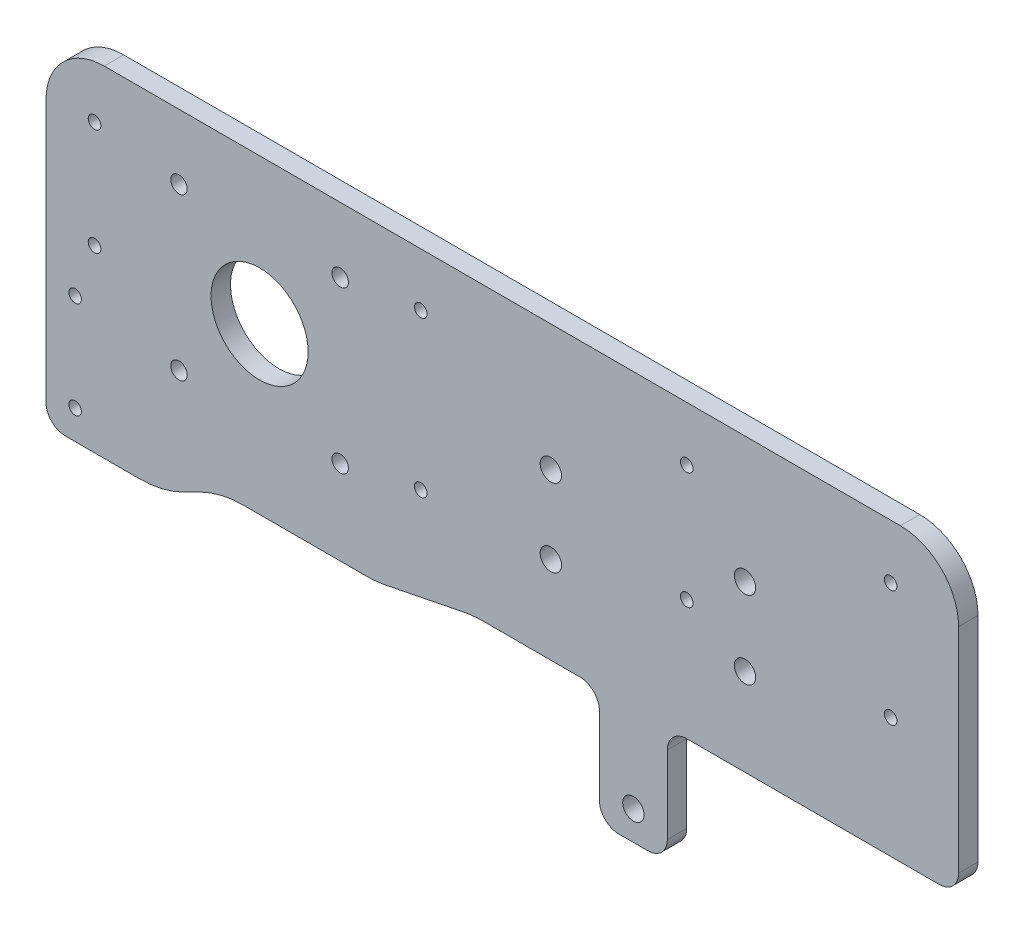
SolidWorks part; units mm, degrees
material "1.4003 (X2CrNi12)"
ref_plane "Ön Düzlem" through (0, 0, 0) normal (0, 0, 1) x (1, 0, 0)
ref_plane "Üst Düzlem" through (0, 0, 0) normal (0, 1, 0) x (1, 0, 0)
ref_plane "Sağ Düzlem" through (0, 0, 0) normal (1, 0, 0) x (0, 0, -1)
sketch "Çizim1" plane through (0, 0, 0) normal (0, 0, 1) x (1, 0, 0)
  line L3 (0, 120) -> (-470, 120)
  line L4 (-380, 0) -> (-380, -40) construction
  line L5 (-380, -40) -> (-300, -40)
  line L6 (-300, -40) -> (-250, -30)
  line L7 (-250, -30) -> (-185, -30)
  line L8 (0, 0) -> (-380, 0) construction
  line L17 (-380, -40) -> (-410, -55)
  line L18 (-410, -55) -> (-470, -55)
  line L24 (-185, -30) -> (-185, -90)
  line L25 (-185, -90) -> (-150, -90)
  line L26 (-150, -90) -> (-150, -30)
  line L27 (-150, -30) -> (0, -30)
  line L28 (0, -30) -> (0, 0)
  line L29 (0, 0) -> (0, 120)
  line L30 (-470, -55) -> (-470, 120)
  point P12 (-340, -40)
  dimension "D8" = 80
  dimension "D2" = 120
  dimension "D3" = 30
  dimension "D4" = 15
  dimension "D5" = 30
  dimension "D6" = 50
  dimension "D7" = 40
  dimension "D9" = 65
  dimension "D10" = 470
  dimension "D11" = 60
  dimension "D12" = 60
  dimension "D13" = 35
base flange "Taban-Flanş1" sketch "Çizim1" thickness 10 reverse thickness direction no parameters "D1"=2
sketch "Çizim2" plane through (0, 0, 0) normal (0, 0, 1) x (1, 0, 0)
  line L0 (0, 0) -> (-233.5345, 0) construction
  line L1 (0, -30) -> (0, 120) construction
  line L2 (0, -30) -> (0, 120) construction
  line L5 (-470, 120) -> (-470, -55) construction
  line L14 (-185, -90) -> (-150, -90) construction
  line L15 (-401.5, 86.5) -> (-318.5, 86.5) construction
  line L16 (-401.5, 86.5) -> (-401.5, 3.5) construction
  line L17 (-401.5, 3.5) -> (-318.5, 3.5) construction
  line L18 (-318.5, 86.5) -> (-318.5, 3.5) construction
  line L19 (-401.5, 86.5) -> (-318.5, 3.5) construction
  line L20 (-401.5, 3.5) -> (-318.5, 86.5) construction
  line L21 (-150, -90) -> (-150, -30) construction
  line L22 (-470, -55) -> (-410, -55) construction
  circle A8 centre (-360, 45) radius 25
  circle A9 centre (-401.5, 86.5) radius 4.25
  circle A10 centre (-318.5, 86.5) radius 4.25
  circle A11 centre (-401.5, 3.5) radius 4.25
  circle A12 centre (-318.5, 3.5) radius 4.25
  circle A13 centre (-110, 55) radius 5.5
  circle A14 centre (-210, 55) radius 5.5
  circle A15 centre (-210, 15) radius 5.5
  circle A16 centre (-110, 15) radius 5.5
  circle A18 centre (-167.5, -75) radius 5.5
  circle A19 centre (-455, 10) radius 3.25
  circle A20 centre (-455, -40) radius 3.25
  dimension "D2" = 45
  dimension "D3" = 40
  dimension "D4" = 100
  dimension "D13" = 50
  dimension "D15" = 360
  dimension "D18" = 8.5
  dimension "D7" = 11
  dimension "D10" = 15
  dimension "D11" = 110
  dimension "D5" = 11
  dimension "D8" = 17.5
  dimension "D9" = 6.5
  dimension "D12" = 50
  dimension "D19" = 15
  dimension "D6" = 15
  dimension "D14" = 15
  dimension "D16" = 83
  dimension "D17" = 83
extrude "Kes-Ekstrüzyon1" cut sketch "Çizim2" against normal blind 10
cosmetic thread "Kozmetik Diş Açma10"
cosmetic thread "Kozmetik Diş Açma11"
cosmetic thread "Kozmetik Diş Açma12"
cosmetic thread "Kozmetik Diş Açma13"
cosmetic thread "Kozmetik Diş Açma14"
cosmetic thread "Kozmetik Diş Açma15"
fillet "Radyus3" radius 30 1 edges at (0, 120, -5)
fillet "Radyus4" radius 10 5 edges at (-185, -30, -5) (-185, -90, -5) (-150, -90, -5) (-150, -30, -5) (0, -30, -5)
fillet "Radyus5" radius 50 4 edges at (-410, -55, -5) (-380, -40, -5) (-300, -40, -5) (-250, -30, -5)
sketch "Çizim3" plane through (0, 0, -10) normal (0, 0, -1) x (-1, 0, 0)
  line L0 (470, 120) -> (470, -55) construction
  line L2 (277, 92.5) -> (277, 12.5) construction
  line L4 (445, 92.5) -> (445, 37.5) construction
  line L6 (30, 120) -> (470, 120) construction
  line L7 (0, -20) -> (0, 90) construction
  line L8 (30, 120) -> (470, 120) construction
  circle A0 centre (277, 92.5) radius 3.25
  circle A1 centre (277, 12.5) radius 3.25
  circle A2 centre (445, 37.5) radius 3.25
  circle A3 centre (445, 92.5) radius 3.25
  circle A4 centre (140, 92) radius 3.25
  circle A5 centre (35, 92) radius 3.25
  circle A6 centre (35, 32) radius 3.25
  circle A7 centre (140, 32) radius 3.25
  point P0 (362.5, 65)
  dimension "D3" = 6.5
  dimension "D5" = 25
  dimension "D6" = 27.5
  dimension "D7" = 6.5
  dimension "D8" = 35
  dimension "D9" = 28
  dimension "D10" = 105
  dimension "D11" = 60
  dimension "D1" = 80
  dimension "D2" = 168
  dimension "D4" = 55
extrude "Kes-Ekstrüzyon2" cut sketch "Çizim3" against normal blind 10
cosmetic thread "Kozmetik Diş Açma2"
cosmetic thread "Kozmetik Diş Açma3"
cosmetic thread "Kozmetik Diş Açma4"
cosmetic thread "Kozmetik Diş Açma5"
cosmetic thread "Kozmetik Diş Açma6"
cosmetic thread "Kozmetik Diş Açma7"
cosmetic thread "Kozmetik Diş Açma8"
cosmetic thread "Kozmetik Diş Açma9"
fillet "Radyus7" radius 10 1 edges at (-470, -55, -5)
fillet "Radyus8" radius 30 1 edges at (-470, 120, -5)
sketch "Büküm-Çizgileri1" [suppressed] plane through (0, 0, 0) normal (0, 1, 0) x (1, 0, 0)
sketch "Sınırlandırma-Kutusu1" [suppressed] plane through (0, 0, 0) normal (0, 1, 0) x (1, 0, 0)
sheet metal parameters "Sac-Levha1" thickness 10 parameters "D1"=2
flat pattern "Düz-Çoğaltma1" [suppressed]
sketch "Büküm-Çizgileri2" plane through (0, 0, 0) normal (0, 1, 0) x (1, 0, 0)
sketch3d "Sınırlandırma-Kutusu2" [suppressed]
  line L0 (-120, -95, 0) -> (336.6856, -95, 0) construction
  line L1 (-120, 95, 0) -> (336.6856, 95, 0) construction
  line L2 (-120, -95, 0) -> (-120, 95, 0) construction
  line L3 (336.6856, -95, 0) -> (336.6856, 95, 0) construction
sheet metal parameters "Sac-Levha2" thickness 10 parameters "D1"=2
flat pattern "Düz-Çoğaltma1" [suppressed]
sketch "Büküm-Çizgileri2" plane through (0, 0, 0) normal (0, 1, 0) x (1, 0, 0)
sketch3d "Sınırlandırma-Kutusu2" [suppressed]
  line L0 (-420, -90, 0) -> (0, -90, 0) construction
  line L1 (-420, 120, 0) -> (0, 120, 0) construction
  line L2 (-420, -90, 0) -> (-420, 120, 0) construction
  line L3 (0, -90, 0) -> (0, 120, 0) construction
sketch "Çizim3-1" plane through (0, 0, -10) normal (0, 0, -1) x (-1, 0, 0)
  line L1 (232.5, 72.5) -> (387.5, 72.5) construction
  line L2 (232.5, 72.5) -> (232.5, 17.5) construction
  line L3 (232.5, 17.5) -> (387.5, 17.5) construction
  line L4 (387.5, 72.5) -> (387.5, 17.5) construction
  line L5 (232.5, 72.5) -> (387.5, 17.5) construction
  line L6 (232.5, 17.5) -> (387.5, 72.5) construction
  circle A0 centre (232.5, 72.5) radius 2.5
  circle A1 centre (232.5, 17.5) radius 2.5
  circle A2 centre (387.5, 17.5) radius 2.5
  circle A3 centre (387.5, 72.5) radius 2.5
  point P0 (310, 45)
  dimension "D3" = 5
  dimension "D1" = 55
  dimension "D2" = 155
sheet metal parameters "Sac-Levha7" thickness 10 parameters "D1"=2
flat pattern "Düz-Çoğaltma1" [suppressed]
sketch "Büküm-Çizgileri2" plane through (0, 0, 0) normal (0, 1, 0) x (1, 0, 0)
sketch3d "Sınırlandırma-Kutusu2" [suppressed]
  line L0 (-470, -90, 0) -> (0, -90, 0) construction
  line L1 (-470, 120, 0) -> (0, 120, 0) construction
  line L2 (-470, -90, 0) -> (-470, 120, 0) construction
  line L3 (0, -90, 0) -> (0, 120, 0) construction
sketch "Çizim3-1" plane through (0, 0, -10) normal (0, 0, -1) x (-1, 0, 0)
  line L0 (470, 90) -> (470, -45) construction
  line L2 (277, 92.5) -> (277, 12.5) construction
  line L4 (445, 92.5) -> (445, 37.5) construction
  line L6 (30, 120) -> (440, 120) construction
  line L7 (0, -20) -> (0, 90) construction
  line L8 (30, 120) -> (440, 120) construction
  circle A0 centre (277, 92.5) radius 3.25
  circle A1 centre (277, 12.5) radius 3.25
  circle A2 centre (445, 37.5) radius 3.25
  circle A3 centre (445, 92.5) radius 3.25
  circle A4 centre (140, 92) radius 3.25
  circle A5 centre (35, 92) radius 3.25
  circle A6 centre (35, 32) radius 3.25
  circle A7 centre (140, 32) radius 3.25
  point P0 (362.5, 65)
  dimension "D3" = 6.5
  dimension "D5" = 25
  dimension "D6" = 27.5
  dimension "D7" = 6.5
  dimension "D8" = 35
  dimension "D9" = 28
  dimension "D10" = 105
  dimension "D11" = 60
  dimension "D1" = 80
  dimension "D2" = 168
  dimension "D4" = 55
